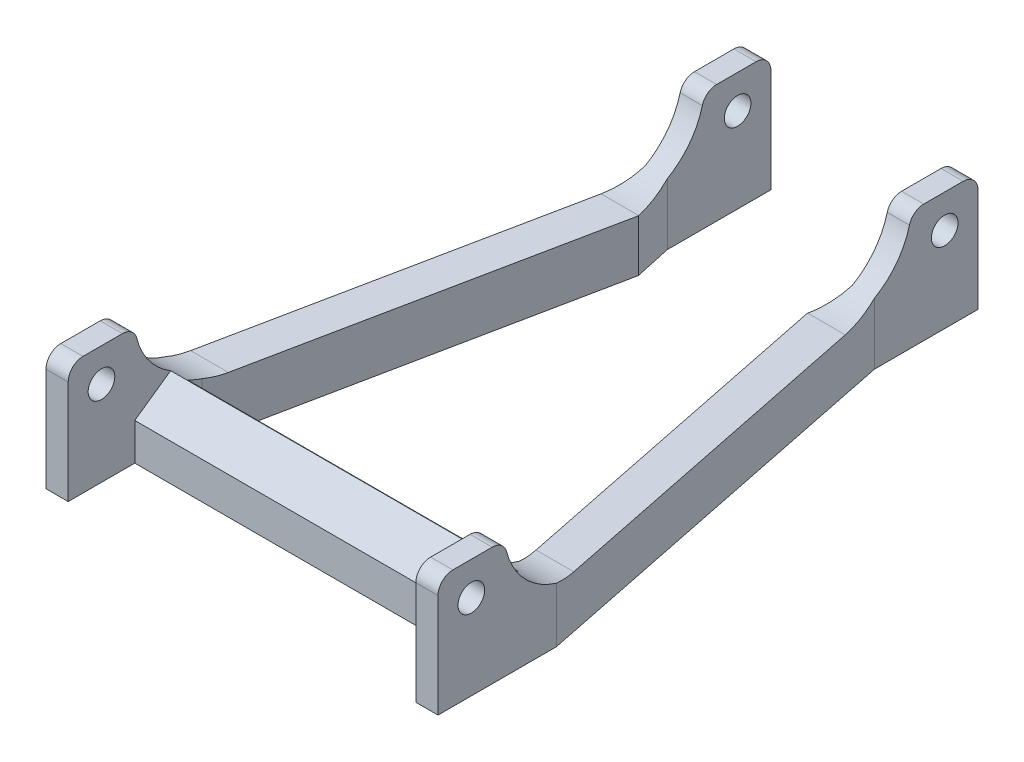
SolidWorks part; units mm, degrees
note: The reader was unsure of these and kept them because the rebuilt part matched: shared geometry of "Sketch1<3>".
material "PLA"
ref_plane "Front Plane" through (0, 0, 0) normal (0, 0, 1) x (1, 0, 0)
ref_plane "Top Plane" through (0, 0, 0) normal (0, 1, 0) x (1, 0, 0)
ref_plane "Right Plane" through (0, 0, 0) normal (1, 0, 0) x (0, 0, -1)
sketch "Sketch1" plane through (0, 0, 0) normal (0, 1, 0) x (1, 0, 0)
  line L0 (-26.5, 0) -> (-26.5, -9)
  line L1 (-26.5, -9) -> (-23.5, -9)
  line L2 (-23.5, -9) -> (-23.5, 0)
  line L3 (-23.5, 0) -> (23.5, 0)
  line L4 (23.5, 0) -> (23.5, -9)
  line L5 (23.5, -9) -> (26.5, -9)
  line L6 (26.5, -9) -> (26.5, 0)
  line L7 (26.5, 0) -> (26.5, 7)
  line L9 (15.5, 66) -> (15.5, 75)
  line L10 (15.5, 75) -> (12.5, 75)
  line L11 (12.5, 75) -> (12.5, 66)
  line L13 (-12.5, 66) -> (-12.5, 75)
  line L14 (-12.5, 75) -> (-15.5, 75)
  line L15 (-15.5, 75) -> (-15.5, 66)
  line L17 (-26.5, 7) -> (-26.5, 0)
  line L18 (-11.4158, 56) -> (-21.3973, 7)
  line L19 (-21.3973, 7) -> (-21.3973, 5)
  line L20 (-21.3973, 5) -> (21.3973, 5)
  line L21 (21.3973, 5) -> (21.3973, 7)
  line L22 (21.3973, 7) -> (11.4158, 56)
  line L23 (11.4158, 56) -> (-11.4158, 56)
  line L24 (-15.5, 66) -> (-12.5, 66)
  line L25 (12.5, 66) -> (15.5, 66)
  line L26 (23.5, 0) -> (26.5, 0)
  line L27 (-23.5, 0) -> (-26.5, 0)
  line L28 (-15.5, 66) -> (-15.5, 61)
  line L29 (-15.5, 61) -> (-26.5, 7)
  line L30 (15.5, 66) -> (15.5, 61)
  line L31 (15.5, 61) -> (26.5, 7)
  line L32 (-12.5, 66) -> (-12.5, 61)
  line L33 (-12.5, 61) -> (12.5, 61)
  line L34 (12.5, 61) -> (12.5, 66)
  line L35 (-11.4158, 56) -> (-12.5, 61)
  line L36 (11.4158, 56) -> (12.5, 61)
  point P17 (0, 0)
  point P29 (0, 61)
  dimension "D1" = 3
  dimension "D2" = 47
  dimension "D3" = 25
  dimension "D4" = 5
  dimension "D5" = 9
  dimension "D6" = 9
  dimension "D7" = 7
  dimension "D8" = 5
  dimension "D9" = 66
  dimension "D10" = 5
  dimension "D11" = 5
  dimension "D12" = 5
extrude "Boss-Extrude1" add sketch "Sketch1" along normal blind 7
extrude "Boss-Extrude2" add sketch "Sketch1<3>" along normal blind 9 from surface at 7 contours L15 L24 L13 L14 | L11 L25 L9 L10 | L2 L27 L0 L1 | L26 L4 L5 L6 starting at face at (0, 7, -29.9091)
sketch "Sketch1<3>" plane through (0, 0, 0) normal (0, 1, 0) x (1, 0, 0) same geometry as "Sketch1"
sketch "Sketch2" plane through (26.5, 0, 0) normal (1, 0, 0) x (0, 0, -1)
  line L0 (-9, 16) -> (0, 7) construction
  line L1 (66, 7) -> (75, 16) construction
  point P8 (70.5, 11.5)
  point P9 (-4.5, 11.5)
hole_wizard "M3 Clearance Hole1" positions "Sketch3" profile "Sketch5" hole size "M3" standard "ISO" end condition through all
sketch "Sketch3" plane through (26.5, 0, 0) normal (1, 0, 0) x (0, 0, -1)
  point P0 (-4.5, 11.5)
  point P3 (70.5, 11.5)
sketch "Sketch5" plane through (26.5, 11.5, 4.5) normal (0, 1, 0) x (0, 0, -1)
  line L0 (0, 0) -> (0, 53)
  line L1 (0, 53) -> (1.8, 53)
  line L2 (1.8, 53) -> (1.8, 0)
  line L5 (1.8, 0) -> (0, 0)
  line L11 (0, -6.35) -> (0, 107.95) construction
  dimension "Thru Hole Dia." = 3.6
  dimension "Thru Hole Depth" = 53
chamfer "Chamfer1" distance 2 angle 55 1 edges at (0, 7, 0)
fillet "Fillet1" radius 10 3 edges at (-25, 7, 0) (14, 7, -66) (-14, 7, -66)
fillet "Fillet2" radius 2 8 edges at (25, 16, 9) (-25, 16, 9) (14, 16, -75) (-14, 16, -75) (14, 16, -66) (-14, 16, -66) (25, 16, 0) (-25, 16, 0)
